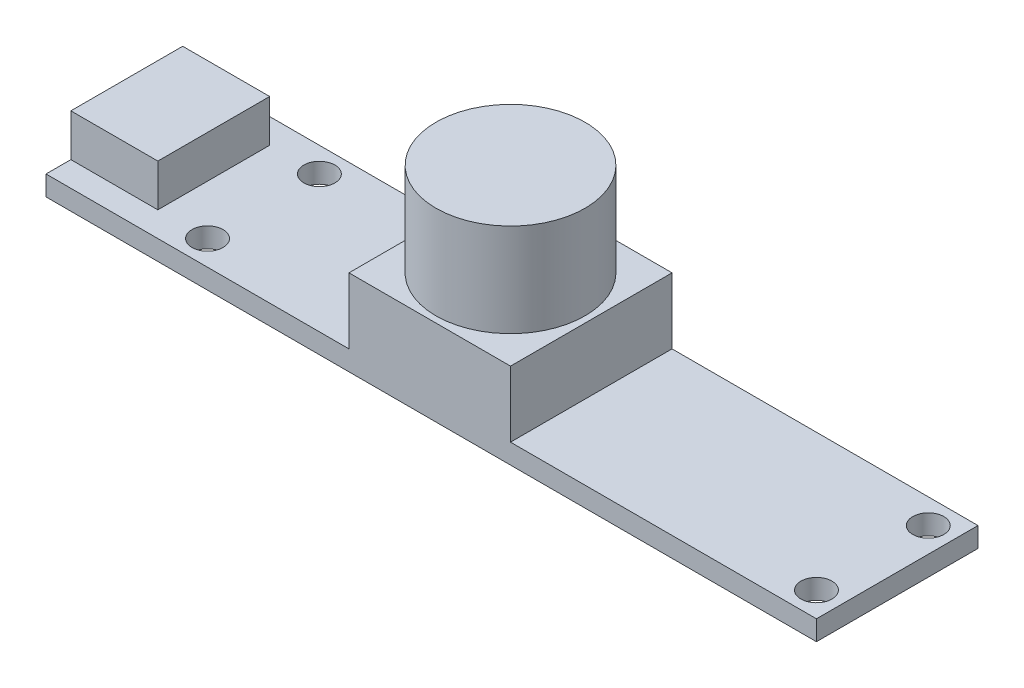
SolidWorks part; units mm, degrees
ref_plane "Front Plane" through (0, 0, 0) normal (0, 0, 1) x (1, 0, 0)
ref_plane "Top Plane" through (0, 0, 0) normal (0, 1, 0) x (1, 0, 0)
ref_plane "Right Plane" through (0, 0, 0) normal (1, 0, 0) x (0, 0, -1)
sketch "Sketch1" plane through (0, 0, 0) normal (0, 1, 0) x (1, 0, 0)
  line L1 (0, 13) -> (62, 13)
  line L2 (0, 13) -> (0, 0)
  line L3 (0, 0) -> (62, 0)
  line L4 (62, 13) -> (62, 0)
  line L5 (24.38, 0) -> (37.38, 0)
  line L6 (24.38, 0) -> (24.38, 13)
  line L7 (24.38, 13) -> (37.38, 13)
  line L8 (37.38, 0) -> (37.38, 13)
  line L9 (24.38, 0) -> (37.38, 13) construction
  line L10 (24.38, 13) -> (37.38, 0) construction
  circle A0 centre (11, 2) radius 1.25
  circle A1 centre (11, 11) radius 1.25
  circle A2 centre (60, 11) radius 1.25
  circle A3 centre (60, 2) radius 1.25
  circle A4 centre (30.88, 6.5) radius 6
  dimension "D3" = 2.5
  dimension "D4" = 11
  dimension "D5" = 2
  dimension "D8" = 2
  dimension "D9" = 12
  dimension "D11" = 6.5
  dimension "D13" = 9
  dimension "D14" = 49
  dimension "D15" = 0
  dimension "D1" = 13
  dimension "D2" = 62
  dimension "D10" = 30.88
  dimension "D12" = 13
  dimension "D6" = 2
  dimension "D7" = 2
extrude "Boss-Extrude1" add sketch "Sketch1" along normal blind 1.6 contours L8 L3 L4 L1 A3 A2 | L3 L6 L1 L2 A1 A0 region at (12.228, 0, -6.5) region at (49.3637, 0, -6.5)
extrude "Boss-Extrude2" add sketch "Sketch1<3>" along normal blind 6.9 contours L3 L8 L1 L6 A4 | A4 region at (30.88, 0, -12.8162)
sketch "Sketch1<3>" plane through (0, 0, 0) normal (0, 1, 0) x (1, 0, 0) same geometry as "Sketch1"
extrude "Boss-Extrude3" add sketch "Sketch1<4>" along normal blind 14.4 contours A4 region at (30.88, 0, -6.5)
sketch "Sketch1<4>" plane through (0, 0, 0) normal (0, 1, 0) x (1, 0, 0) same geometry as "Sketch1"
sketch "Sketch3" plane through (0, 1.6, 0) normal (0, 1, 0) x (1, 0, 0)
  line L0 (0, 13) -> (0, 0) construction
  line L1 (0, 11) -> (7, 11)
  line L2 (0, 11) -> (0, 2)
  line L3 (0, 2) -> (7, 2)
  line L4 (7, 11) -> (7, 2)
  line L5 (0, 0) -> (24.38, 0) construction
  dimension "D1" = 2
  dimension "D2" = 9
  dimension "D3" = 7
extrude "Boss-Extrude4" add sketch "Sketch3" along normal blind 3.4
